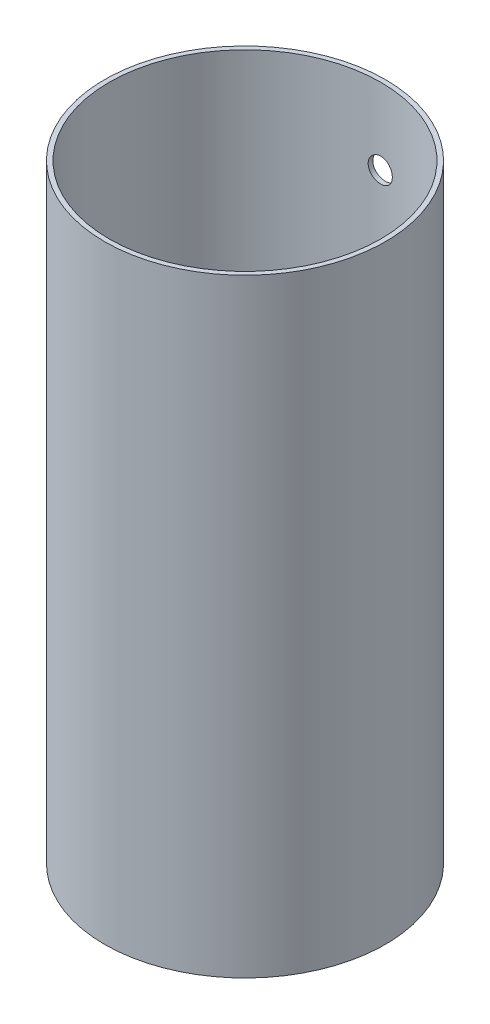
SolidWorks part; units mm, degrees
material "A-Glass Fiber"
ref_plane "Front Plane" through (0, 0, 0) normal (0, 0, 1) x (1, 0, 0)
ref_plane "Top Plane" through (0, 0, 0) normal (0, 1, 0) x (1, 0, 0)
ref_plane "Right Plane" through (0, 0, 0) normal (1, 0, 0) x (0, 0, -1)
sketch "Sketch1" plane through (0, 0, 0) normal (0, 1, 0) x (1, 0, 0)
  circle A0 centre (0, 0) radius 76.1746
  circle A1 centre (0, 0) radius 73.66
  dimension "D1" = 152.3492
  dimension "D2" = 147.32
extrude "Boss-Extrude1" add sketch "Sketch1" along normal blind 330.2
sketch "Sketch4" plane through (0, 0, 0) normal (0, 0, 1) x (1, 0, 0)
  line L0 (-76.1746, 0) -> (76.1746, 0) construction
  line L1 (76.1746, 330.2) -> (-76.1746, 330.2) construction
  point P0 (0, 41.275)
  point P3 (0, 288.925)
  dimension "D1" = 41.275
  dimension "D2" = 41.275
hole_wizard "1/2 Clearance Hole5" positions "Sketch16" profile "Sketch17" hole size "1/2" standard "ANSI Inch"
sketch "Sketch16" plane through (0, 0, 0) normal (0, 0, 1) x (1, 0, 0)
  point P0 (0, 288.925)
sketch "Sketch17" plane through (0, 288.925, 0) normal (1, 0, 0) x (0, -1, 0)
  line L0 (0, 0) -> (0, 80.1345)
  line L1 (0, 80.1345) -> (6.5481, 76.2)
  line L2 (6.5481, 76.2) -> (6.5481, 0)
  line L5 (6.5481, 0) -> (0, 0)
  line L10 (0, 80.1345) -> (-6.5481, 76.2) construction
  line L11 (0, -6.35) -> (0, 107.95) construction
  dimension "Hole Dia." = 13.0962
  dimension "Hole Depth" = 76.2
  dimension "Drill Angle" = 118
hole_wizard "1/2 Clearance Hole7" positions "Sketch20" profile "Sketch21" hole size "1/2" standard "ANSI Inch"
sketch "Sketch20" plane through (0, 0, 0) normal (0, 0, 1) x (1, 0, 0)
  point P0 (0, 41.275)
sketch "Sketch21" plane through (0, 41.275, 0) normal (1, 0, 0) x (0, -1, 0)
  line L0 (0, 0) -> (0, 80.1345)
  line L1 (0, 80.1345) -> (6.5481, 76.2)
  line L2 (6.5481, 76.2) -> (6.5481, 0)
  line L5 (6.5481, 0) -> (0, 0)
  line L10 (0, 80.1345) -> (-6.5481, 76.2) construction
  line L11 (0, -6.35) -> (0, 107.95) construction
  dimension "Hole Dia." = 13.0962
  dimension "Hole Depth" = 76.2
  dimension "Drill Angle" = 118
equation "\"Mid_Coupler_Length\" = 13in"
equation "\"D1@Boss-Extrude1\"=\"Mid_Coupler_Length\""
